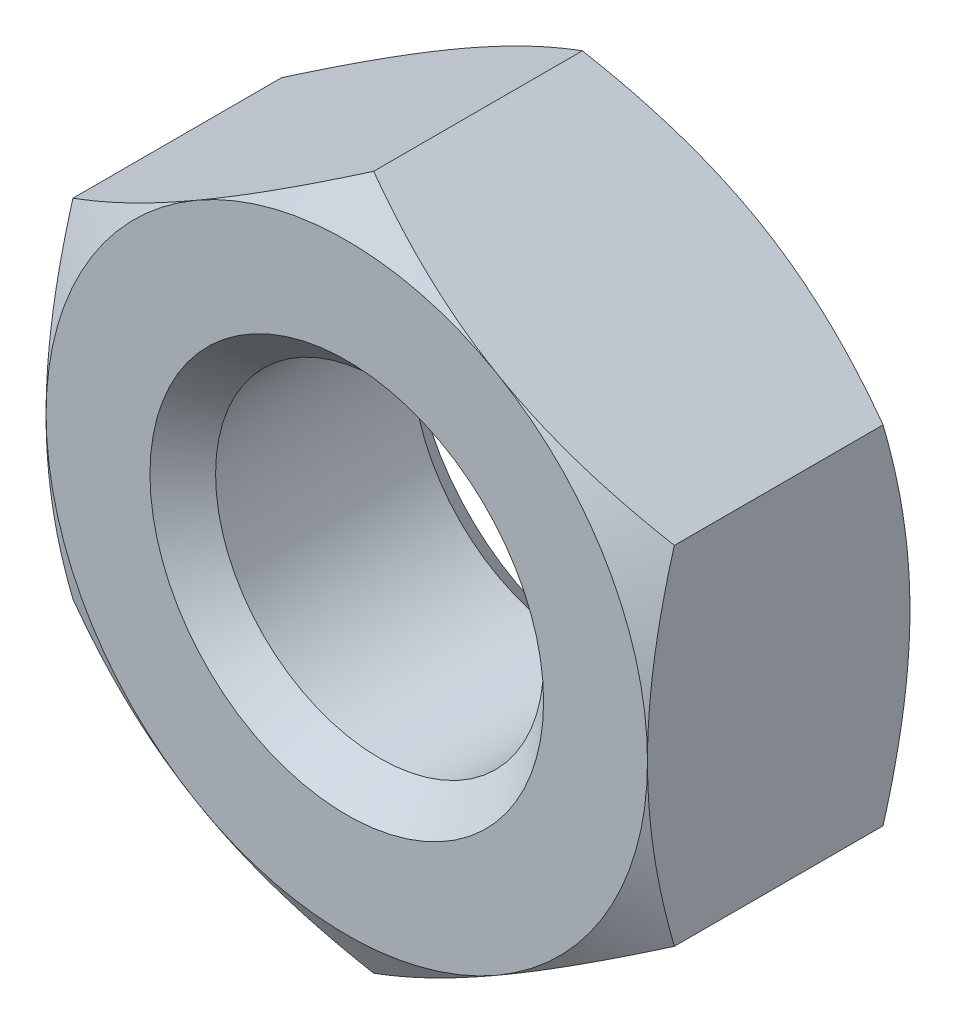
SolidWorks part; units mm, degrees
material "AISI Type A2 Tool Steel"
ref_plane "Front Plane" through (0, 0, 0) normal (0, 0, 1) x (1, 0, 0)
ref_plane "Top Plane" through (0, 0, 0) normal (0, 1, 0) x (1, 0, 0)
ref_plane "Right Plane" through (0, 0, 0) normal (1, 0, 0) x (0, 0, -1)
sketch "Sketch1" plane through (0, 0, 0) normal (0, 0, 1) x (1, 0, 0)
  line L1 (0, 3.1754) -> (-2.75, 1.5877)
  line L2 (-2.75, 1.5877) -> (-2.75, -1.5877)
  line L3 (-2.75, -1.5877) -> (0, -3.1754)
  line L4 (0, -3.1754) -> (2.75, -1.5877)
  line L5 (2.75, -1.5877) -> (2.75, 1.5877)
  line L6 (2.75, 1.5877) -> (0, 3.1754)
  circle A0 centre (0, 0) radius 2.75 construction
  circle A1 centre (0, 0) radius 1.5
  circle A3 centre (0, 0) radius 3.75
  dimension "D1" = 7.5
  dimension "D2" = 5.5
  dimension "D3" = 3
extrude "Boss-Extrude1" add sketch "Sketch1" along normal blind 2.4 contours A3 L6 L5 L4 L3 L2 L1 | L5 L6 L1 L2 L3 L4 A1 region at (1.333, 2.3088, 0) region at (-3.6439, 0, 0)
chamfer "Chamfer1" distance 1 angle 30 1 edges at (3.75, 0, 2.4) first distance on face at (3.75, 0, 2.4)
chamfer "Chamfer2" distance 1 angle 30 1 edges at (3.75, 0, 0) first distance on face at (3.75, 0, 0)
extrude "Cut-Extrude1" cut sketch "Sketch1<3>" along normal through all contours A3 L6 L5 L4 L3 L2 L1 region at (-3.6439, 0, 0)
sketch "Sketch1<3>" plane through (0, 0, 0) normal (0, 0, 1) x (1, 0, 0) same geometry as "Sketch1"
chamfer "Chamfer3" distance 0.3 angle 45 2 edges at (1.5, 0, 0) (1.5, 0, 2.4)
